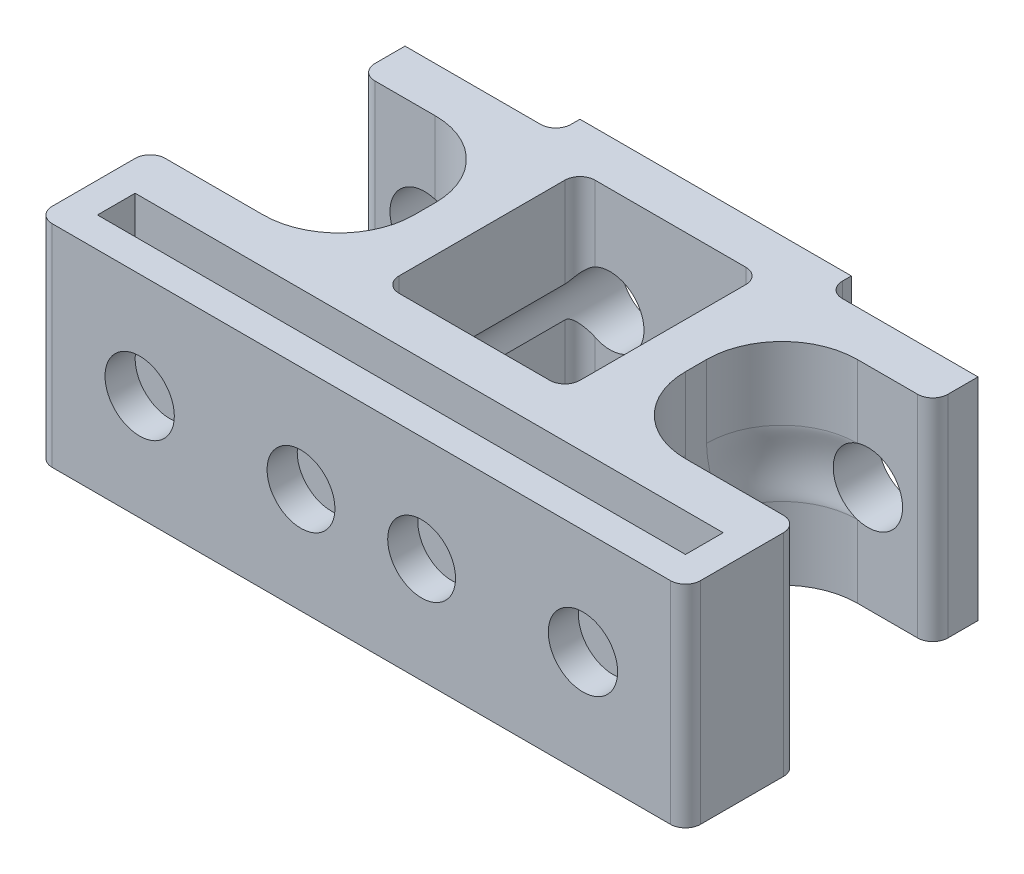
SolidWorks part; units mm, degrees
ref_plane "Front Plane" through (0, 0, 0) normal (0, 0, 1) x (1, 0, 0)
ref_plane "Top Plane" through (0, 0, 0) normal (0, 1, 0) x (1, 0, 0)
ref_plane "Right Plane" through (0, 0, 0) normal (1, 0, 0) x (0, 0, -1)
sketch "Sketch1" plane through (0, 0, 0) normal (0, 1, 0) x (1, 0, 0)
  line L0 (18, 17.4) -> (28, 17.4)
  line L1 (0, 0) -> (18, 0)
  line L2 (0, 0) -> (0, 19)
  line L3 (0, 19) -> (18, 19)
  line L4 (18, 0) -> (18, 19)
  line L5 (28, 17.4) -> (28, 14.4)
  line L6 (28, 14.4) -> (18, 14.4)
  line L7 (0, 17.4) -> (-10, 17.4)
  line L8 (-10, 17.4) -> (-10, 14.4)
  line L9 (-10, 14.4) -> (0, 14.4)
  line L10 (18, 0) -> (28.5, 0)
  line L11 (-10.5, -2.5) -> (28.5, -2.5)
  line L12 (-12.5, 3) -> (0, 3)
  line L13 (18, 3) -> (30.5, 3)
  line L14 (-10.5, 0) -> (0, 0)
  line L15 (0, 3) -> (18, 3)
  line L21 (28.5, -2.5) -> (28.5, 0)
  line L22 (-10.5, 0) -> (-10.5, -2.5)
  line L25 (-12.5, 3) -> (-12.5, -4.5)
  line L26 (-12.5, -4.5) -> (30.5, -4.5)
  line L27 (30.5, -4.5) -> (30.5, 3)
  point P28 (9, -4.5)
  point P29 (9, 3)
  dimension "D1" = 19
  dimension "D2" = 18
  dimension "D3" = 1.6
  dimension "D4" = 3
  dimension "D5" = 10
  dimension "D6" = 10
  dimension "D7" = 3
  dimension "D8" = 2
  dimension "D9" = 2
  dimension "D10" = 2.5
  dimension "D11" = 2
  dimension "D12" = 39
extrude "Boss-Extrude1" add sketch "Sketch1" along normal blind 14 contours L8 L9 L2 L7 | L2 L15 L4 L3 | L6 L5 L0 L4 | L15 L2 L1 L4 | L26 L27 L13 L4 L10 L21 L11 L22 L14 L2 L12 L25 region at (23, 0, -15.9) region at (9, 0, -11) region at (24.25, 0, -2.5635) region at (9, 0, -1.5) region at (-5, 0, -15.9)
sketch "Sketch2" plane through (0, 0, 0) normal (0, 0, 1) x (1, 0, 0)
  line L0 (28.5, 14) -> (28.5, 0) construction
  line L1 (-10.5, 14) -> (-10.5, 0) construction
  circle A0 centre (23.7, 7) radius 2.3
  circle A1 centre (-5.7, 7) radius 2.3
  point P8 (0, 0)
  point P9 (28.5, 7)
  dimension "D1" = 4.8
  dimension "D3" = 4.6
  dimension "D4" = 4.6
  dimension "D2" = 4.8
extrude "Cut-Extrude1" cut sketch "Sketch2" against normal through all both and the other way through all
sketch "Sketch3" plane through (0, 0, 0) normal (0, -1, 0) x (1, 0, 0)
  line L0 (0, -19) -> (18, -19) construction
  line L1 (15, -16) -> (3, -16)
  line L2 (15, -16) -> (15, -3)
  line L3 (15, -3) -> (3, -3)
  line L4 (3, -16) -> (3, -3)
  line L5 (-10.5, 0) -> (28.5, 0) construction
  line L6 (0, -3) -> (0, -14.4) construction
  line L7 (18, -3) -> (18, -14.4) construction
  dimension "D1" = 3
  dimension "D2" = 3
  dimension "D3" = 3
  dimension "D4" = 3
extrude "Cut-Extrude2" cut sketch "Sketch3" against normal through all
sketch "Sketch4" plane through (0, 0, -19) normal (0, 0, -1) x (-1, 0, 0)
  line L0 (0, 14) -> (0, 0) construction
  line L2 (-13, 7) -> (-5, 7) construction
  line L3 (0, 0) -> (-18, 0) construction
  circle A0 centre (-5, 7) radius 2.25
  circle A1 centre (-13, 7) radius 2.25
  point P4 (-9, 7)
  point P7 (0, 7)
  point P10 (-9, 0)
  point P11 (-12.5499, 7)
  dimension "D1" = 4.5
  dimension "D2" = 4.5
  dimension "D3" = 8
extrude "Cut-Extrude3" cut sketch "Sketch4" against normal through all both and the other way through all
fillet "Fillet1" radius 5 4 edges at (0, 7, -3) (0, 7, -14.4) (18, 7, -3) (18, 7, -14.4)
fillet "Fillet2" radius 1 16 edges at (18, 7, -17.4) (0, 7, -17.4) (28, 7, -14.4) (-10, 7, -14.4) (-12.5, 7, 4.5) (-12.5, 7, -3) (30.5, 7, 4.5) (30.5, 7, -3) (3, 11.0154, -3) (3, 2.9846, -3) (15, 2.9846, -3) (15, 11.0154, -3) (3, 11.0154, -16) (3, 2.9846, -16) (15, 11.0154, -16) (15, 2.9846, -16)
